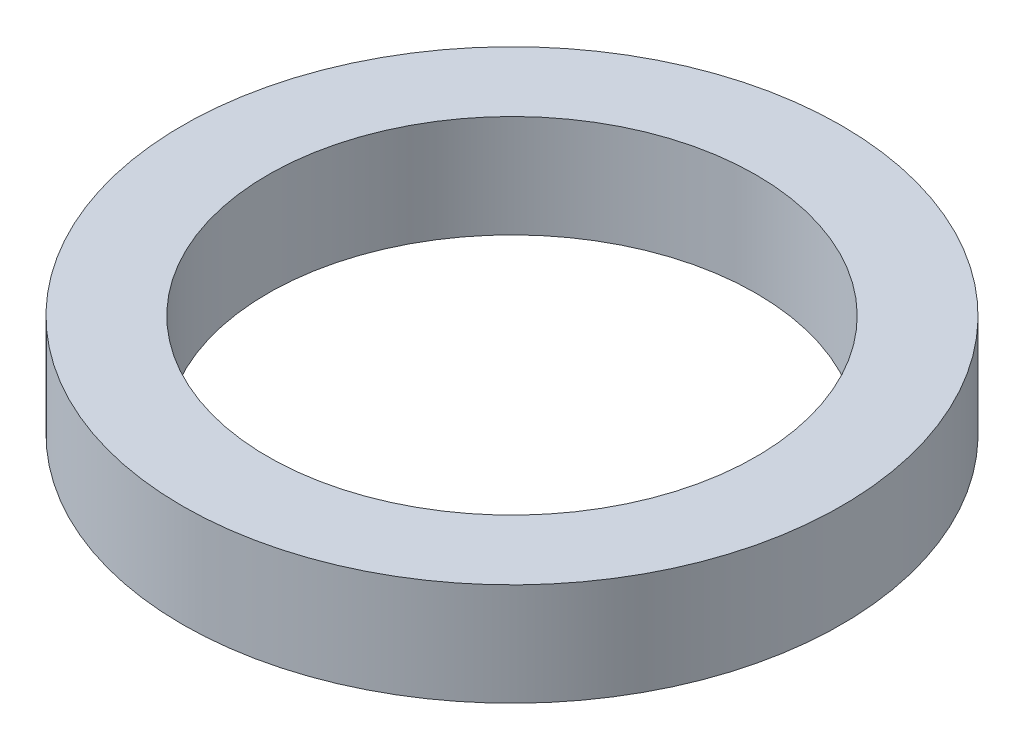
SolidWorks part; units mm, degrees
ref_plane "Front Plane" through (0, 0, 0) normal (0, 0, 1) x (1, 0, 0)
ref_plane "Top Plane" through (0, 0, 0) normal (0, 1, 0) x (1, 0, 0)
ref_plane "Right Plane" through (0, 0, 0) normal (1, 0, 0) x (0, 0, -1)
sketch "Sketch1" plane through (0, 0, 0) normal (0, 1, 0) x (1, 0, 0)
  circle A0 centre (0, 0) radius 67.5
  dimension "FLANGE_OD" = 135
extrude "Boss-Extrude1" add sketch "Sketch1" along normal blind 21
sketch "Sketch2" plane through (0, 0, 0) normal (0, 1, 0) x (1, 0, 0)
  circle A0 centre (0, 0) radius 50
  dimension "BORE_D" = 100
extrude "Cut-Extrude1" cut sketch "Sketch2" along normal through all
sketch "Sketch3" plane through (0, 21, 0) normal (0, 1, 0) x (1, 0, 0)
  circle A0 centre (0, 0) radius 27.4748 construction
  circle A1 centre (-27.4748, 0) radius 2.9264
  dimension "BOLT_D" = 5.8527
  dimension "BOLT_PCD" = 54.9496
extrude "Cut-Extrude2" cut sketch "Sketch3" against normal blind 16.0906 rebuild error yes
pattern_circular "CirPattern1" count 3 over 360 rebuild error yes
